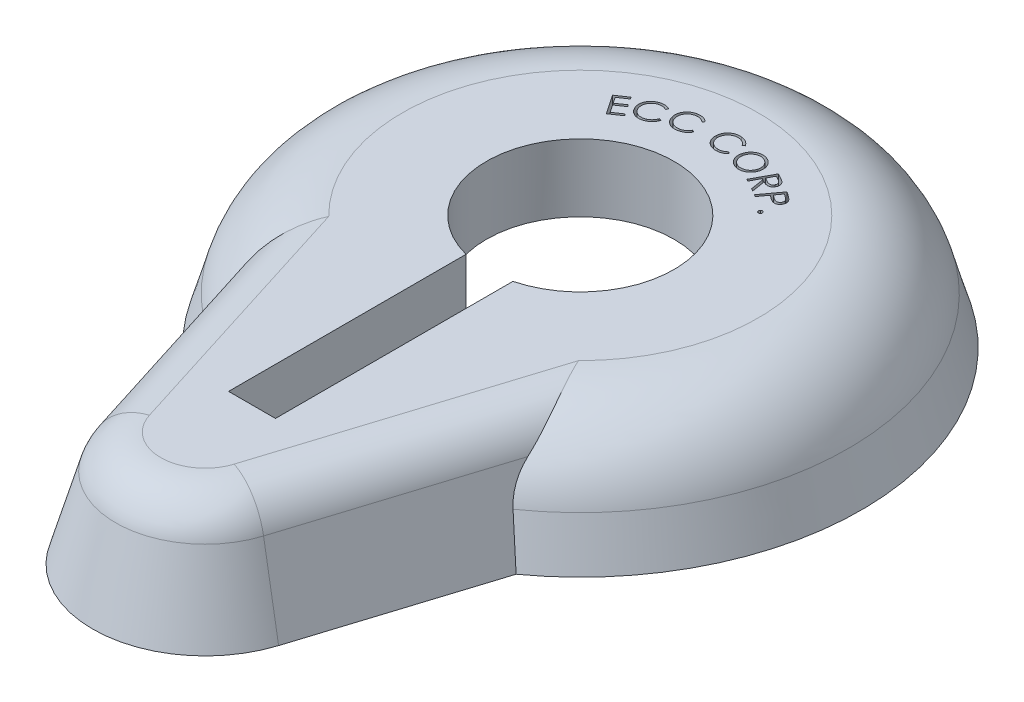
SolidWorks part; units mm, degrees
ref_plane "Front Plane" through (0, 0, 0) normal (0, 0, 1) x (1, 0, 0)
ref_plane "Top Plane" through (0, 0, 0) normal (0, 1, 0) x (1, 0, 0)
ref_plane "Right Plane" through (0, 0, 0) normal (1, 0, 0) x (0, 0, -1)
sketch "Sketch2" plane through (0, 0, 0) normal (0, 1, 0) x (1, 0, 0)
  line L1 (0, 0) -> (0, 45.9932) construction
  line L2 (-22.2438, 19.8674) -> (-14.5346, -4.5828)
  line L3 (22.2438, 19.8674) -> (14.5346, -4.5828)
  arc A0 (-14.5346, -4.5828) -> (14.5346, -4.5828) centre (0, 0) ccw
  arc A3 (-22.2438, 19.8674) -> (22.2438, 19.8674) centre (0, 50.8) cw
  point P9 (0, -0.842)
  point P11 (-1.1272, -20.6083)
  dimension "D1" = 15.24
  dimension "D2" = 38.1
  dimension "D3" = 50.8
  dimension "D4" = 35
extrude "Boss-Extrude1" add sketch "Sketch2" along normal blind 15.494 draft 16
fillet "Fillet1" radius 6.35 3 edges at (14.3818, 15.494, -9.7071) (0, 15.494, 10.7972) (-14.3818, 15.494, -9.7071)
fillet "Fillet2" radius 12.7 1 edges at (0, 15.494, -84.4572)
sketch "Sketch6" plane through (0, 0, 0) normal (0, -1, 0) x (1, 0, 0)
  line L4 (20.0801, -21.4521) -> (12.1122, 3.819)
  line L5 (-12.1122, 3.819) -> (-20.0801, -21.4521)
  line L6 (20.0801, -21.4521) -> (12.1122, 3.819)
  line L7 (-12.1122, 3.819) -> (-20.0801, -21.4521)
  arc A4 (-20.0801, -21.4521) -> (20.0801, -21.4521) centre (0, -50.8) ccw
  arc A5 (12.1122, 3.819) -> (-12.1122, 3.819) centre (0, 0) ccw
  arc A6 (-20.0801, -21.4521) -> (20.0801, -21.4521) centre (0, -50.8) ccw
  arc A7 (12.1122, 3.819) -> (-12.1122, 3.819) centre (0, 0) ccw
  dimension "D1" = 2.54
extrude "Cut-Extrude3" cut sketch "Sketch6" against normal blind 6.35 draft 16 contours A6 L6 A7 L7
sketch "Sketch7" plane through (0, 15.494, 0) normal (0, 1, 0) x (1, 0, 0)
  circle A0 centre (0, 50.8) radius 12.7
extrude "Cut-Extrude4" cut sketch "Sketch7" against normal through all
sketch "Sketch8" plane through (0, 15.494, 0) normal (0, 1, 0) x (1, 0, 0)
  line L0 (0, 57.15) -> (0, 0) construction
  line L1 (-3.175, 57.15) -> (3.175, 57.15)
  line L2 (-3.175, 57.15) -> (-3.175, 6.35)
  line L3 (-3.175, 6.35) -> (3.175, 6.35)
  line L4 (3.175, 57.15) -> (3.175, 6.35)
  point P6 (0, 0)
  dimension "D1" = 6.35
  dimension "D2" = 50.8
  dimension "D3" = 6.35
extrude "Cut-Extrude5" cut sketch "Sketch8" against normal blind 6.35
sketch "Sketch15" plane through (0, 15.494, 0) normal (0, 1, 0) x (1, 0, 0)
  arc A0 (16.0848, 56.4892) -> (-15.2809, 58.3885) centre (0, 50.8) ccw construction
  text T0 "ECC CORP."
extrude "Cut-Extrude8" cut sketch "Sketch15" against normal blind 1.27
